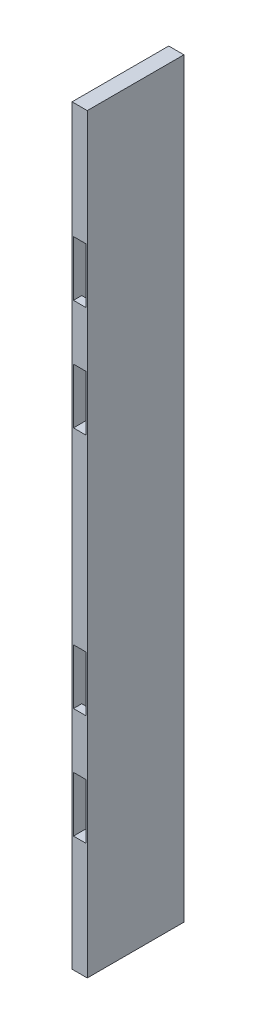
SolidWorks part; units mm, degrees
ref_plane "Top" through (0, 0, 0) normal (0, 0, 1) x (1, 0, 0)
ref_plane "Front" through (0, 0, 0) normal (0, 1, 0) x (1, 0, 0)
ref_plane "Right" through (0, 0, 0) normal (1, 0, 0) x (0, 0, -1)
sketch "Profile Sketch" plane through (0.0456, 0, -0.0242) normal (0, 1, 0) x (-1, 0, 0)
  line L0 (2.5456, -17.4758) -> (2.5456, 0.0242)
  line L1 (2.5456, 0.0242) -> (0.0456, 0.0242)
  line L2 (0.0456, 0.0242) -> (0.0456, -17.4758)
  line L3 (0.0456, -17.4758) -> (2.5456, -17.4758)
  line L12 (2.2956, 0.0242) -> (2.2956, -17.4758) construction
  dimension "D1" = 17.5
  dimension "D3" = 2.25
  dimension "Cover Thickness" = 0.25
extrude "Profile Extrude" add sketch "Profile Sketch" along normal blind 136
ref_plane "Mid Plane" through (0, 68, 0) normal (0, -1, 0) x (-1, 0, 0)
ref_plane "Right Cut Out Location" through (0, 36, 0) normal (0, -1, 0) x (-1, 0, 0)
ref_plane "Left Cut Out Location" through (0, 100, 0) normal (0, -1, 0) x (-1, 0, 0)
sketch "Cover Latch Cut Out Sketch" plane through (-2.5, 0, 0) normal (-1, 0, 0) x (0, 0, 1)
  line L4 (-17.5, 43) -> (-17.5, 29)
  line L5 (0, 31) -> (-1.5, 31)
  line L10 (0, 41) -> (0, 31) construction
  line L11 (0, 136) -> (0, 0) construction
  line L12 (-1.5, 31) -> (-2.1583, 36)
  line L13 (-2.1583, 36) -> (-1.5, 41)
  line L14 (-1.5, 41) -> (0, 41)
  line L15 (-2.1583, 36) -> (0, 36) construction
  line L16 (0, 41) -> (0, 51)
  line L17 (0, 51) -> (-8.1583, 51)
  line L18 (0, 31) -> (0, 21)
  line L21 (0, 21) -> (-8.1583, 21)
  line L22 (-8.1583, 51) -> (-8.1583, 43)
  line L23 (-8.1583, 43) -> (-17.5, 43)
  line L24 (-8.1583, 21) -> (-8.1583, 29)
  line L25 (-8.1583, 29) -> (-17.5, 29)
  line L27 (-17.5, 136) -> (-17.5, 0) construction
  point P3 (0, 68)
  dimension "D1" = 1.5
  dimension "D2" = 10
  dimension "D3" = 10
  dimension "D4" = 7.5
  dimension "D5" = 6
  dimension "Latch Position" = 32
extrude "Cover Latch Cut Out" cut sketch "Cover Latch Cut Out Sketch" against normal blind 2.25
mirror "Cover Latch Cut Out Mirror" about plane through (0, 68, 0) normal (0, -1, 0) of "Cover Latch Cut Out"
sketch "Side Sketch" plane through (0, 0, 0) normal (0, 1, 0) x (1, 0, 0)
  line L7 (-2.75, 17.5) -> (-2.5, 17.5)
  line L8 (-2.75, 17.5) -> (-2.75, 0)
  line L9 (-2.75, 0) -> (-2.5, 0)
  line L10 (-2.5, 17.5) -> (-2.5, 0)
  dimension "Cover Thickness" = 0.25
extrude "Side Extrude" add sketch "Side Sketch" along normal through all
